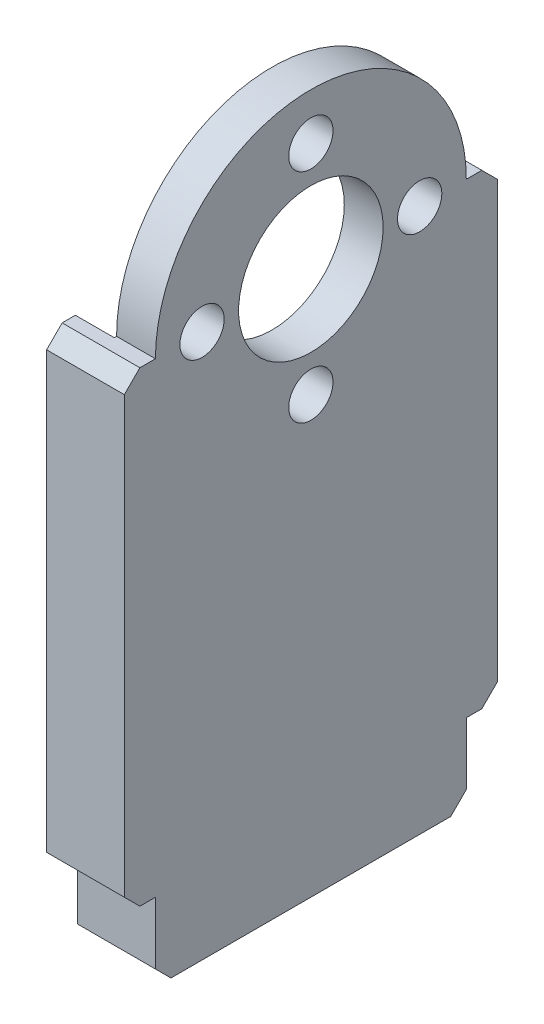
SolidWorks part; units mm, degrees
ref_plane "Front Plane" through (0, 0, 0) normal (0, 0, 1) x (1, 0, 0)
ref_plane "Top Plane" through (0, 0, 0) normal (0, 1, 0) x (1, 0, 0)
ref_plane "Right Plane" through (0, 0, 0) normal (1, 0, 0) x (0, 0, -1)
sketch "Sketch1" plane through (0, 0, 0) normal (1, 0, 0) x (0, 0, -1)
  line L1 (-10, 30) -> (10, 30) construction
  line L2 (-10, 30) -> (-10, 0)
  line L3 (-10, 0) -> (10, 0)
  line L4 (10, 30) -> (10, 0)
  line L5 (-10, 30) -> (10, 0) construction
  line L6 (-10, 0) -> (10, 30) construction
  circle A0 centre (0, 30) radius 10
  circle A1 centre (0, 30) radius 4.5
  circle A3 centre (7, 30) radius 1.275
  circle A6 centre (0, 30) radius 1
  circle A7 centre (0, 23) radius 1.275
  circle A8 centre (-7, 30) radius 1.275
  circle A9 centre (0, 37) radius 1.275
  point P0 (0, 15)
  dimension "D1" = 20
  dimension "D2" = 2.55
  dimension "D4" = 2
  dimension "D5" = 9
  dimension "D3" = 7
  dimension "D6" = 4
  dimension "D7" = 30
extrude "Boss-Extrude1" add sketch "Sketch1" against normal blind 2.5 contours A0 A3 A1 region at (0, 39.7172, 0)
extrude "Boss-Extrude3" add sketch "Sketch1<6>" against normal blind 5 contours A0 L2 L3 L4 region at (0, 11.1855, 0)
sketch "Sketch1<6>" plane through (0, 0, 0) normal (1, 0, 0) x (0, 0, -1) same geometry as "Sketch1"
sketch "Sketch2" plane through (0, 0, 0) normal (0, -1, 0) x (1, 0, 0)
  line L4 (0, -10) -> (0, 10)
  line L5 (0, 10) -> (-5, 10)
  line L6 (-5, 10) -> (-5, -10)
  line L7 (-5, -10) -> (0, -10)
  line L8 (0, -10) -> (0, 10)
  line L9 (0, 10) -> (-5, 10)
  line L10 (-5, 10) -> (-5, -10)
  line L11 (-5, -10) -> (0, -10)
  dimension "D1" = 0
extrude "Boss-Extrude4" add sketch "Sketch2" along normal blind 5 separate body
combine bodies "Combine2" operation type add bodies to combine 103 105
sketch "Sketch3" plane through (0, 0, 0) normal (1, 0, 0) x (0, 0, -1)
  line L0 (10, 0) -> (12, 0)
  line L1 (-10, 30) -> (-12, 30)
  line L2 (-10, 30) -> (-10, -5)
  line L3 (-10, 30) -> (-10, -5)
  line L4 (-10, -5) -> (10, -5)
  line L5 (10, -5) -> (10, 30)
  line L6 (-10, 30) -> (-10, -5)
  line L7 (-10, -5) -> (10, -5)
  line L8 (10, -5) -> (10, 30)
  line L9 (-10, -5) -> (-12, -5) construction
  line L10 (-12, 30) -> (-12, -5)
  line L11 (10, -5) -> (12, -5) construction
  line L12 (10, -5) -> (10, 30)
  line L13 (10, 30) -> (12, 30)
  line L14 (12, -5) -> (12, 30)
  line L15 (-10, 0) -> (-12, 0)
  arc A1 (10, 30) -> (-10, 30) centre (0, 30) ccw
  arc A2 (10, 30) -> (-10, 30) centre (0, 30) ccw
  point P13 (0, 0)
  point P14 (0, 0)
  line M13 (-10, 30) -> (-10, -5)
  line M15 (10, -5) -> (10, 30)
  dimension "D2" = 2
  dimension "D3" = 5
  dimension "D1" = 0
extrude "Boss-Extrude5" add sketch "Sketch3" against normal up to surface (5 mm away) contours L11 L14 L13 M15 | L1 L10 L9 M13 region at (0, 15, -11) region at (0, 15, 11) up to face at (-5, 10, 0)
chamfer "Chamfer1" distance 1 angle 45 4 edges at (-2.5, 0, -12) (-2.5, 0, 12) (-2.5, 30, -12) (-2.5, 30, 12)
chamfer "Chamfer2" distance 1 angle 45 2 edges at (-2.5, -5, -10) (-2.5, -5, 10)
other "Offset for 3D print" flip direction yes face at (-3.75, 25, 0) face at (-2.5, 37, -1.275) face at (-2.5, 23, -1.275) face at (-2.5, 30, -8.275) face at (-2.5, 30, 5.725) face at (-2.5, 30, -4.5) offset 0.15 parameters "D1"=0.15
